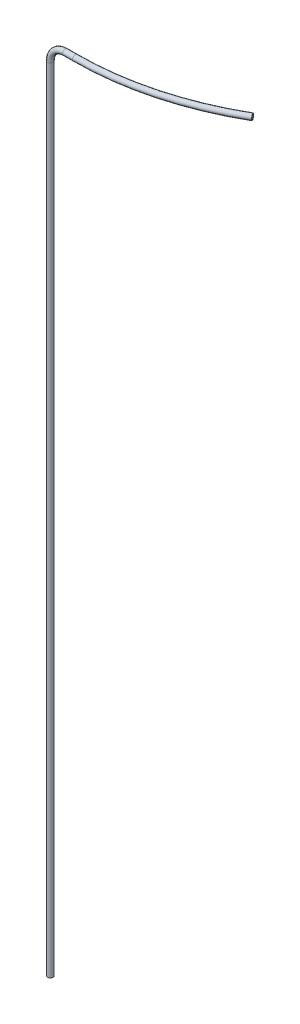
SolidWorks part; units mm, degrees
note: '?' marks a value the reader was unsure of.
other "标注1"
sketch "草图12" plane through (303, -1732.7423, -1294) normal (0.0011, -0.9938, 0.1111) x (-0.9676, -0.0291, -0.2508)
ref_plane "前视基准面" through (0, 0, 0) normal (0, 0, 1) x (1, 0, 0)
ref_plane "上视基准面" through (0, 0, 0) normal (0, 1, 0) x (1, 0, 0)
ref_plane "右视基准面" through (0, 0, 0) normal (1, 0, 0) x (0, 0, -1)
sketch "草图10" plane through (0, 0, 0) normal (0, 1, 0) x (1, 0, 0)
  line L0 (0, 0) -> (0, 1900)
ref_axis "基准轴3" through (0, 0, -1900) along (0, 1, 0)
sketch "草图1" plane through (0, 0, 0) normal (1, 0, 0) x (0, 0, -1)
  line L0 (1300, -0.3711) -> (0, 0)
  line L1 (0, 139.1195) -> (0, -57.917) construction
  circle A0 centre (1300, -0.3711) radius 6
  circle A1 centre (1300, -0.3711) radius 4
  dimension "D1" = 12
  dimension "D2" = 8
  dimension "D3" = 1300
revolve "旋转1" add sketch "草图1" angle 30 about axis through (0, 0, -1900) along (0, 1, 0)
sketch "草图2" plane through (0, 0, 0) normal (-1, 0, 0) x (0, 0, 1)
  line L0 (-500, -31.0864) -> (-500, 27.4301) construction
  circle A0 centre (-500, -0.3711) radius 10
  circle A1 centre (-500, -0.3711) radius 15
  circle A4 centre (-1300, -0.3711) radius 4
  circle A5 centre (-1300, -0.3711) radius 6
ref_plane "基准面1" through (0, 0, -500) normal (0, 0, -1) x (0, 1, 0)
sketch "草图3" plane through (0, 0, -500) normal (0, 0, -1) x (0, 1, 0)
  line L0 (0, 0) -> (0, -21.3411)
  line L1 (-32.7423, -54.0834) -> (-932.7423, -54.0834)
  arc A0 (0, -21.3411) -> (-32.7423, -54.0834) centre (-32.7423, -21.3411) cw
  dimension "D1" = 900
sweep "扫描1" add profiles "草图2" path "草图3"
sketch "草图5" plane through (0, 0, 0) normal (1, 0, 0) x (0, 0, -1)
  line L0 (0, 0) -> (1300, 0)
  line L1 (1300, 0) -> (1300, 54.7405)
ref_axis "基准轴1" through (0, 0, -1300) along (0, 1, 0)?
ref_plane "基准面2" through (0, 0, -1300) normal (0, 0, -1) x (-1, 0, 0)
sketch "草图6" plane through (0, 0, 0) normal (0, 1, 0) x (1, 0, 0)
  line L0 (0, 1294) -> (0, 1306)
  line L2 (-21.3411, 1294) -> (-21.3411, 1306) construction
  point P0 (-53.7124, 1300)
  point P9 (-21.3411, 1300)
  point P13 (0, 1300)
sketch "草图11" plane through (0, -932.7423, 0) normal (0, -1, 0) x (1, 0, 0)
  circle A0 centre (-53.7124, -1300) radius 4 construction
  circle A1 centre (-53.7124, -1300) radius 6
  circle A2 centre (-53.7124, -1300) radius 6
  circle A3 centre (-53.7124, -1300) radius 4
  dimension "D1" = 0
extrude "凸台-拉伸1" add sketch "草图11" along normal blind 800
